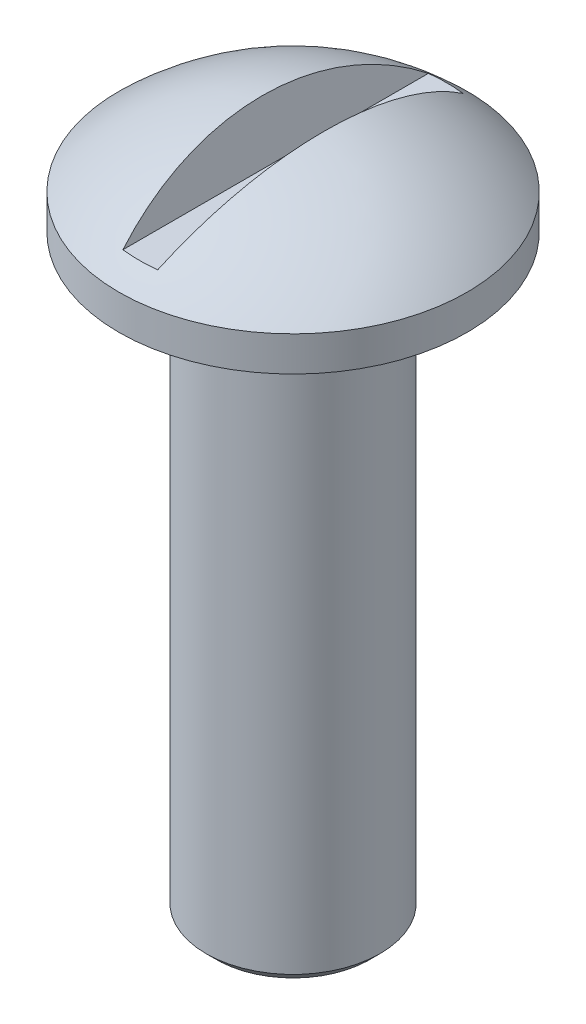
SolidWorks part; units mm, degrees
ref_plane "Front Plane" through (0, 0, 0) normal (0, 0, 1) x (1, 0, 0)
ref_plane "Top Plane" through (0, 0, 0) normal (0, 1, 0) x (1, 0, 0)
ref_plane "Right Plane" through (0, 0, 0) normal (1, 0, 0) x (0, 0, -1)
sketch "Sketch2" plane through (0, 0, 0) normal (0, 0, 1) x (1, 0, 0)
  line L0 (0, 0) -> (-0.5, 0)
  line L1 (-0.5, 0) -> (-0.5, -0.1)
  line L2 (-0.5, -0.1) -> (-0.25, -0.1)
  line L3 (-0.25, -0.1) -> (-0.25, -1.8)
  line L4 (-0.25, -1.8) -> (0, -1.8)
  line L5 (0, -1.8) -> (0, 0)
  line L9 (0, 0.3416) -> (0, -3.0187) construction
  point P11 (0, 0)
  point P14 (0, 0)
  dimension "D2" = 1.8
  dimension "D3" = 0.1
  dimension "D5" = 0.25
  dimension "D6" = 0.5
revolve "Revolve5" add sketch "Sketch2" angle 360 about L9
dome "Dome1" faces to dome 1 distance 0.2 reverse direction no elliptical dome no face at (0, 0, 0.5) parameters "D1"=0.2
sketch "Sketch3" plane through (0, 0, 0) normal (0, 0, 1) x (1, 0, 0)
  line L0 (0.05, 0.05) -> (-0.05, 0.05)
  line L1 (-0.05, 0.05) -> (-0.0887, 0.1945)
  line L2 (0, 0.3311) -> (0, -0.3134) construction
  line L3 (0.05, 0.05) -> (0.0887, 0.1945)
  arc A0 (0.5, 0) -> (-0.5, 0) centre (0, -0.525) ccw construction
  point P9 (0, 0.05)
  dimension "D1" = 0.05
  dimension "D2" = 0.15
  dimension "D3" = 15
extrude "Cut-Extrude1" cut sketch "Sketch3" against normal through all both and the other way through all flip side to cut
chamfer "Chamfer1" distance 0.03 angle 45 1 edges at (0, -1.8, 0.25)
